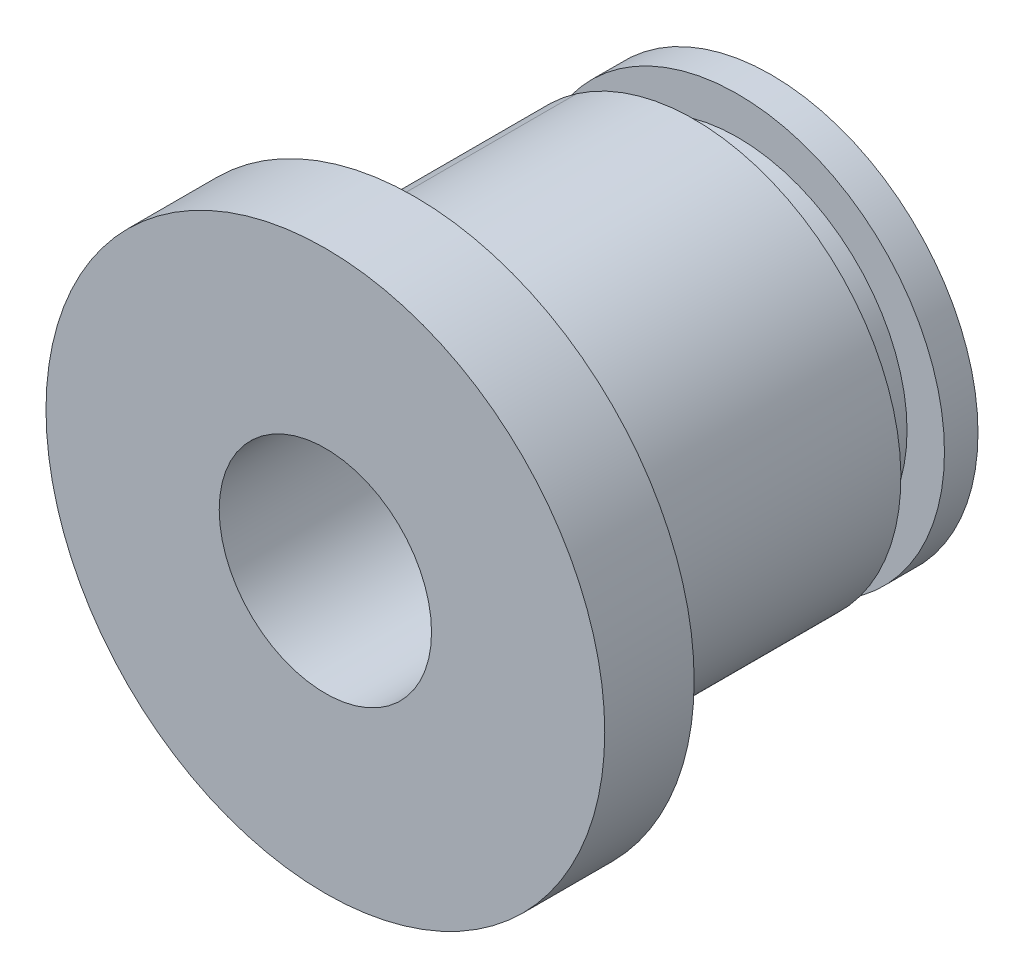
SolidWorks part; units mm, degrees
material "AISI 4130 Steel, annealed at 865C"
ref_plane "Front Plane" through (0, 0, 0) normal (0, 0, 1) x (1, 0, 0)
ref_plane "Top Plane" through (0, 0, 0) normal (0, 1, 0) x (1, 0, 0)
ref_plane "Right Plane" through (0, 0, 0) normal (1, 0, 0) x (0, 0, -1)
sketch "Sketch1" plane through (0, 0, 0) normal (0, 0, 1) x (1, 0, 0)
  circle A0 centre (0, 0) radius 6.35
  dimension "D1" = 12.7
extrude "Boss-Extrude1" add sketch "Sketch1" along normal blind 2.032
sketch "Sketch2" plane through (0, 0, 0) normal (0, 0, -1) x (-1, 0, 0)
  circle A0 centre (0, 0) radius 4.699
  dimension "D1" = 9.398
extrude "Boss-Extrude2" add sketch "Sketch2" along normal blind 8.1026
ref_axis "Axis1" through (0, 0, 6.5491) along (0, 0, -1)
sketch "Sketch4" plane through (0, 0, 0) normal (1, 0, 0) x (0, 0, -1)
  line L0 (0, -4.699) -> (0, 4.699) construction
  line L1 (0, -4.699) -> (0, 4.699)
  line L2 (6.35, 4.699) -> (6.35, -4.699)
  line L3 (8.1026, 4.699) -> (0, 4.699) construction
  line L4 (0, -4.699) -> (8.1026, -4.699) construction
  line L5 (0, 4.699) -> (8.1026, 4.699)
  line L6 (0, -4.699) -> (8.1026, -4.699)
  line L7 (8.1026, -4.699) -> (8.1026, 4.699) construction
  line L8 (7.3406, 4.699) -> (7.3406, -4.699)
  line L9 (6.35, 3.8481) -> (7.3406, 3.8481)
  line L10 (6.35, 0) -> (7.3406, 0)
  dimension "D1" = 6.35
  dimension "D2" = 0.9906
  dimension "D3" = 3.8481
revolve "Cut-Revolve1" cut sketch "Sketch4" angle 360 about axis through (0, 0, 6.5491) along (0, 0, -1) region at (0, 4.2736, -6.8453)
sketch3d "3DSketch1"
  line L0 (2.6418, -3.886, 0) -> (-2.6678, 3.8683, 0)
  circle A2 centre (0, 0, 0) radius 4.699 construction
  point P4 (0, 0, -4.699)
split line "Split Line3"
sketch "Sketch8" plane through (0, 0, 2.032) normal (0, 0, 1) x (1, 0, 0)
  circle A0 centre (0, 0) radius 2.413
extrude "Cut-Extrude2" cut sketch "Sketch8" against normal blind 15.24
